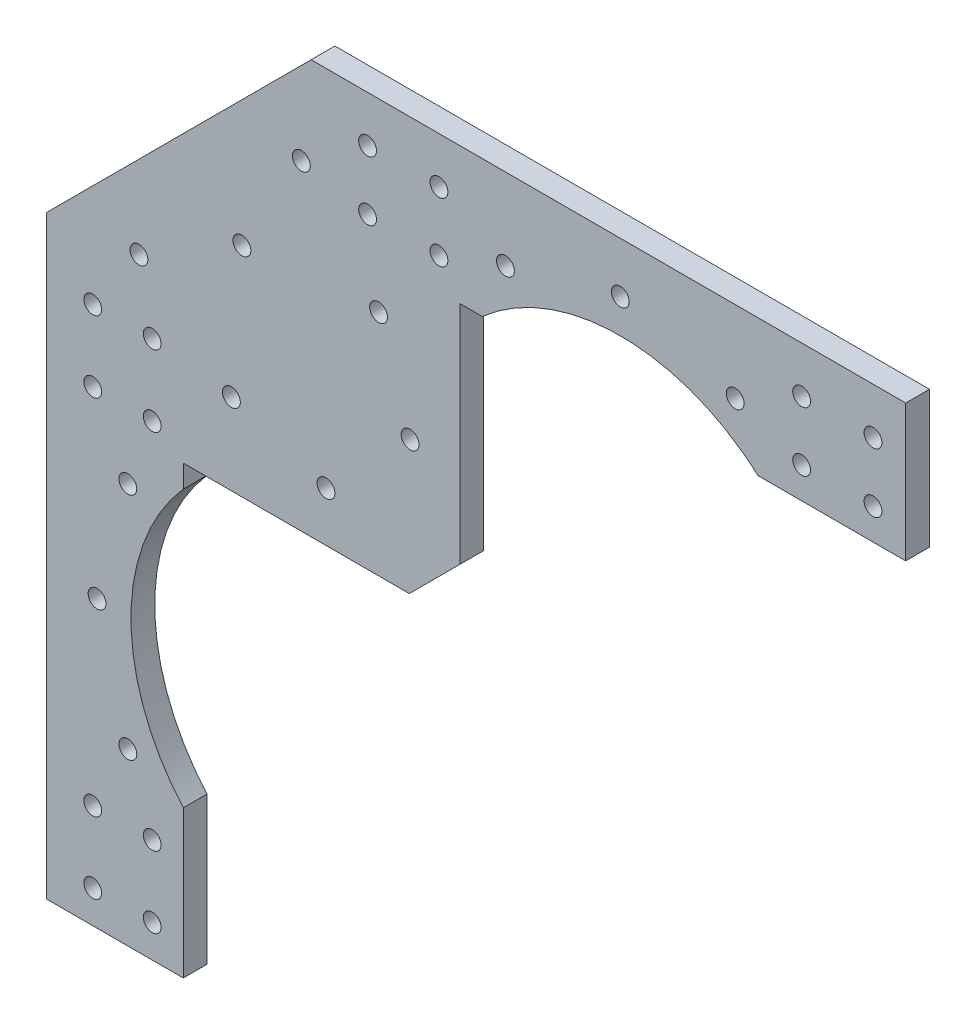
SolidWorks part; units mm, degrees
ref_plane "Front Plane" through (0, 0, 0) normal (0, 0, 1) x (1, 0, 0)
ref_plane "Top Plane" through (0, 0, 0) normal (0, 1, 0) x (1, 0, 0)
ref_plane "Right Plane" through (0, 0, 0) normal (1, 0, 0) x (0, 0, -1)
sketch "Sketch1" plane through (0, 0, 0) normal (0, 0, 1) x (1, 0, 0)
  line L0 (0, 0) -> (0, 73.5) construction
  line L1 (-96.5, -48) -> (-73.5, -48)
  line L2 (-96.5, -48) -> (-96.5, 52)
  line L4 (-73.5, -48) -> (-73.5, 27) construction
  line L5 (-52, 96.5) -> (48, 96.5)
  line L7 (-27, 73.5) -> (48, 73.5) construction
  line L8 (48, 96.5) -> (48, 73.5)
  line L9 (0, 0) -> (-73.5, 0) construction
  line L10 (-27, 73.5) -> (-73.5, 27) construction
  line L11 (-73.5, 73.5) -> (-27, 73.5) construction
  line L12 (-73.5, 27) -> (-73.5, 73.5) construction
  line L13 (-52, 96.5) -> (-96.5, 52)
  line L14 (-96.5, 96.5) -> (-52, 96.5) construction
  line L15 (-96.5, 52) -> (-96.5, 96.5) construction
  line L16 (-23.2069, 73.5) -> (-27, 73.5)
  line L17 (23.2069, 73.5) -> (48, 73.5)
  line L18 (-73.5, 27) -> (-73.5, 23.2069)
  line L19 (-73.5, -48) -> (-73.5, -23.2069)
  line L20 (-73.5, 23.2069) -> (-73.5, -23.2069) construction
  line L21 (-23.2069, 73.5) -> (23.2069, 73.5) construction
  line L22 (-73.5, 27) -> (-35.4853, 27)
  line L23 (-27, 35.4853) -> (-27, 73.5)
  line L24 (-35.4853, 27) -> (-27, 35.4853)
  arc A0 (23.2069, 73.5) -> (-23.2069, 73.5) centre (0, 47.3) ccw
  arc A1 (-73.5, 23.2069) -> (-73.5, -23.2069) centre (-47.3, 0) ccw
  dimension "D6" = 35
  dimension "D1" = 135
  dimension "D2" = 23
  dimension "D3" = 73.5
  dimension "D4" = 48
  dimension "D8" = 27
  dimension "D9" = 12
  dimension "D5" = 100
  dimension "D7" = 26.2
extrude "Boss-Extrude1" add sketch "Sketch1" along normal blind 4
ref_axis "Axis1" through (0, 0, -0.2) along (0, 0, 1)
sketch "Sketch3" plane through (0, 0, 4) normal (0, 0, 1) x (1, 0, 0)
  line L1 (30.5, 88.7259) -> (30.5, 78.7259) construction
  line L2 (30.5, 88.7259) -> (42.5, 88.7259) construction
  line L3 (42.5, 88.7259) -> (42.5, 78.7259) construction
  line L4 (30.5, 78.7259) -> (42.5, 78.7259) construction
  line L16 (-30.5, 78.7259) -> (0, 78.7259) construction
  line L17 (0, 78.7259) -> (0, 0) construction
  line L18 (0, 78.7259) -> (30.5, 78.7259) construction
  line L19 (-78.7259, 0) -> (0, 0) construction
  line L20 (-78.7259, -30.5) -> (-78.7259, 0) construction
  line L21 (-78.7259, 0) -> (-78.7259, 30.5) construction
  line L30 (-42.5, 88.7259) -> (-42.5, 78.7259) construction
  line L31 (-42.5, 88.7259) -> (-30.5, 88.7259) construction
  line L32 (-30.5, 88.7259) -> (-30.5, 78.7259) construction
  line L33 (-42.5, 78.7259) -> (-30.5, 78.7259) construction
  line L34 (-88.7259, 42.5) -> (-88.7259, 30.5) construction
  line L35 (-88.7259, 42.5) -> (-78.7259, 42.5) construction
  line L36 (-78.7259, 42.5) -> (-78.7259, 30.5) construction
  line L37 (-88.7259, 30.5) -> (-78.7259, 30.5) construction
  line L38 (-88.7259, -30.5) -> (-88.7259, -42.5) construction
  line L39 (-88.7259, -30.5) -> (-78.7259, -30.5) construction
  line L40 (-78.7259, -30.5) -> (-78.7259, -42.5) construction
  line L41 (-88.7259, -42.5) -> (-78.7259, -42.5) construction
  circle A0 centre (30.5, 78.7259) radius 1.5
  circle A1 centre (30.5, 88.7259) radius 1.5
  circle A2 centre (42.5, 88.7259) radius 1.5
  circle A3 centre (42.5, 78.7259) radius 1.5
  circle A24 centre (-42.5, 78.7259) radius 1.5
  circle A25 centre (-42.5, 88.7259) radius 1.5
  circle A26 centre (-30.5, 88.7259) radius 1.5
  circle A27 centre (-30.5, 78.7259) radius 1.5
  circle A28 centre (-88.7259, 30.5) radius 1.5
  circle A29 centre (-88.7259, 42.5) radius 1.5
  circle A30 centre (-78.7259, 42.5) radius 1.5
  circle A31 centre (-78.7259, 30.5) radius 1.5
  circle A32 centre (-88.7259, -42.5) radius 1.5
  circle A33 centre (-88.7259, -30.5) radius 1.5
  circle A34 centre (-78.7259, -30.5) radius 1.5
  circle A35 centre (-78.7259, -42.5) radius 1.5
  dimension "D1" = 3
  dimension "D8" = 30.5
  dimension "D2" = 12
  dimension "D6" = 10
  dimension "D3" = 78.7259
extrude "Cut-Extrude1" cut sketch "Sketch3" against normal blind 10
sketch "Sketch4" plane through (0, 0, 4) normal (0, 0, 1) x (1, 0, 0)
  line L0 (0, 0) -> (0, 88) construction
  line L1 (0, 0) -> (-63.6396, 63.6396) construction
  line L2 (0, 0) -> (-88, 0) construction
  line L3 (-82.8236, 19.3185) -> (-88, 0) construction
  line L4 (-88, 0) -> (-82.8236, -19.3185) construction
  line L5 (-80.9601, 53.6396) -> (-63.6396, 63.6396) construction
  line L6 (-63.6396, 63.6396) -> (-83.2677, 83.2677) construction
  line L7 (-19.3185, 82.8236) -> (0, 88) construction
  line L8 (-65.4074, 40.6586) -> (-40.6586, 65.4074) construction
  line L9 (-35.3553, 49.4975) -> (-49.4975, 35.3553) construction
  line L10 (-73.5, -48) -> (-73.5, -23.2069) construction
  line L11 (-35.4853, 27) -> (-27, 35.4853) construction
  circle A0 centre (-88, 0) radius 1.5
  circle A1 centre (-63.6396, 63.6396) radius 1.5
  circle A2 centre (0, 88) radius 1.5
  circle A3 centre (-80.9601, 53.6396) radius 1.5
  circle A4 centre (-53.6396, 80.9601) radius 1.5
  circle A5 centre (19.3185, 82.8236) radius 1.5
  circle A6 centre (-19.3185, 82.8236) radius 1.5
  circle A7 centre (-82.8236, 19.3185) radius 1.5
  circle A8 centre (-82.8236, -19.3185) radius 1.5
  circle A9 centre (-40.6586, 65.4074) radius 1.5
  circle A10 centre (-65.4074, 40.6586) radius 1.5
  circle A11 centre (-49.4975, 35.3553) radius 1.5
  circle A12 centre (-35.3553, 49.4975) radius 1.5
  dimension "D2" = 3
  dimension "D1" = 45
  dimension "D3" = 14.5
  dimension "D4" = 75
  dimension "D5" = 20
  dimension "D6" = 45.8162
  dimension "D7" = 75
  dimension "D8" = 75
  dimension "D9" = 35
  dimension "D10" = 20
  dimension "D11" = 15
  dimension "D12" = 15
extrude "Cut-Extrude2" cut sketch "Sketch4" against normal through all
equation "\"EyeDiameter\" = 35"
equation "\"BasePlaneDistance\" = \"EyeDiameter\"/2+19.84"
equation "\"EyeClearance\" = 2"
equation "\"L2Thickness\" = 8"
equation "\"L2_ID\" = 20"
equation "\"Offset\"= - 2"
equation "\"D3@Sketch1\"=\"BasePlaneDistance\" + 38.16 +\"Offset\""
equation "\"D3@Sketch3\"=\"BasePlaneDistance\" - 37.34+78.72592343"
equation "\"D7@Sketch1\"=24.20 - \"Offset\""
equation "\"D2@Sketch1\"=25.00 + \"Offset\""
